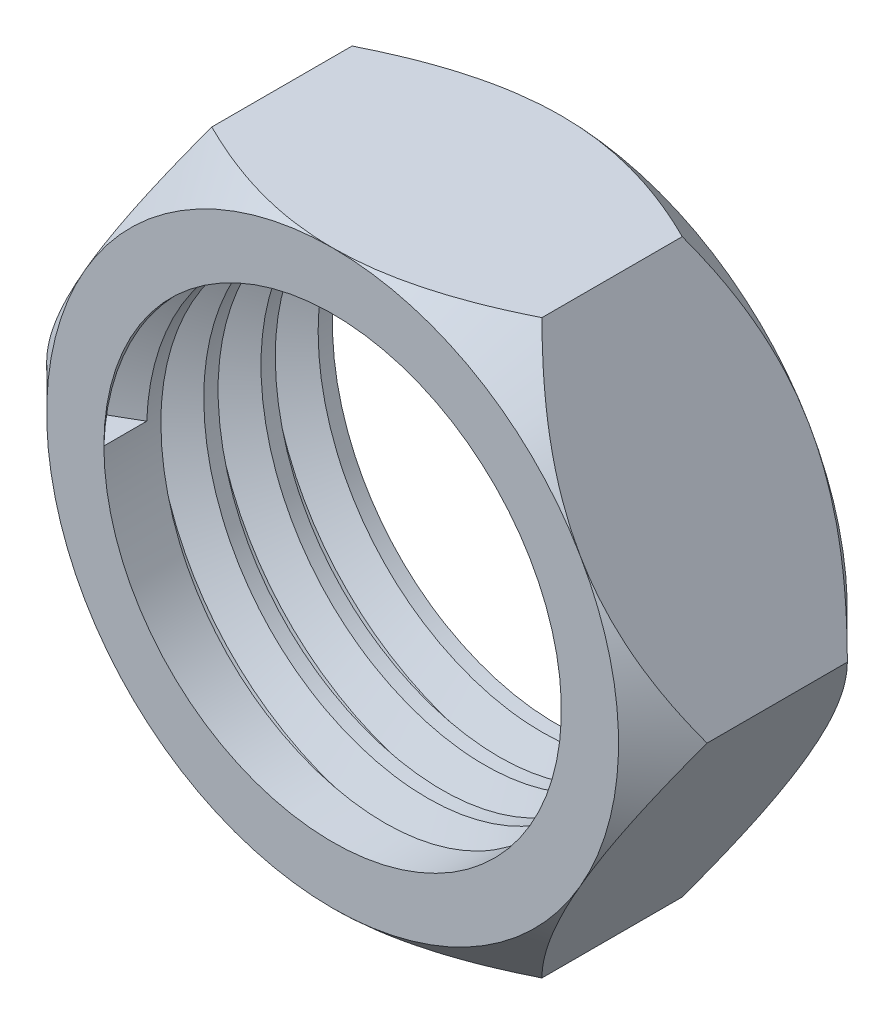
SolidWorks part; units mm, degrees
ref_plane "Front Plane" through (0, 0, 0) normal (0, 0, 1) x (1, 0, 0)
ref_plane "Top Plane" through (0, 0, 0) normal (0, 1, 0) x (1, 0, 0)
ref_plane "Right Plane" through (0, 0, 0) normal (1, 0, 0) x (0, 0, -1)
sketch "Sketch1" plane through (0, 0, 0) normal (0, 0, 1) x (1, 0, 0)
  line L0 (-1.4434, 0) -> (1.4434, 0) construction
  line L1 (1.4434, 0) -> (0.7217, 1.25)
  line L2 (0.7217, 1.25) -> (-0.7217, 1.25)
  line L3 (-0.7217, 1.25) -> (-1.4434, 0)
  line L4 (-1.4434, 0) -> (-0.7217, -1.25)
  line L5 (-0.7217, -1.25) -> (0.7217, -1.25)
  line L6 (0.7217, -1.25) -> (1.4434, 0)
  line L7 (0, -1.25) -> (0, 1.25) construction
  circle A0 centre (0, 0) radius 1.25
  circle A1 centre (0, 0) radius 1
  dimension "D1" = 2.5
  dimension "D2" = 2
extrude "Boss-Extrude1" add sketch "Sketch1" along normal blind 1 contours L3 L4 L5 L6 L1 L2
extrude "Cut-Extrude1" cut sketch "Sketch1<3>" along normal up to next contours A1
sketch "Sketch1<3>" plane through (0, 0, 0) normal (0, 0, 1) x (1, 0, 0) same geometry as "Sketch1"
extrude "Cut-Extrude2" cut sketch "Sketch1<4>" along normal blind 1 draft 45 flip side to cut contours A0
sketch "Sketch1<4>" plane through (0, 0, 0) normal (0, 0, 1) x (1, 0, 0) same geometry as "Sketch1"
ref_plane "Plane1" through (0, 0, 1) normal (0, 0, 1) x (1, 0, 0)
sketch "Sketch2" plane through (0, 0, 1) normal (0, 0, 1) x (1, 0, 0)
  circle A0 centre (0, 0) radius 1.25
  dimension "D1" = 2.5
extrude "Cut-Extrude3" cut sketch "Sketch2" against normal blind 1 draft 45 flip side to cut
thread "Thread1" pitch 0.25 method cut profile "Thread Profile1" start angle 0, offset 0, length 0, pitch 0.25, diameter 2
ref_plane "Plane2" through (-1, 0, 1) normal (0, -1, 0) x (-1, 0, 0)
sketch "Thread Profile1" plane through (-1, 0, 1) normal (0, -1, 0) x (-1, 0, 0)
  line L0 (0, 0) -> (0, 0.25) construction
  line L1 (0, 0) -> (0.1353, 0.0781)
  line L2 (0.1353, 0.0781) -> (0.1353, 0.1094)
  line L3 (0.1353, 0.1094) -> (0, 0.1875)
  line L4 (0.1353, 0.0937) -> (0, 0.0937) construction
  line L11 (0, 0) -> (0, 0.1875)
  point P2 (0, 0)
  dimension "Pitch" = 0.25
  dimension "Profile_Angle" = 60
  dimension "Profile_Land" = 0.0312
  dimension "Profile_Height" = 0.1353
